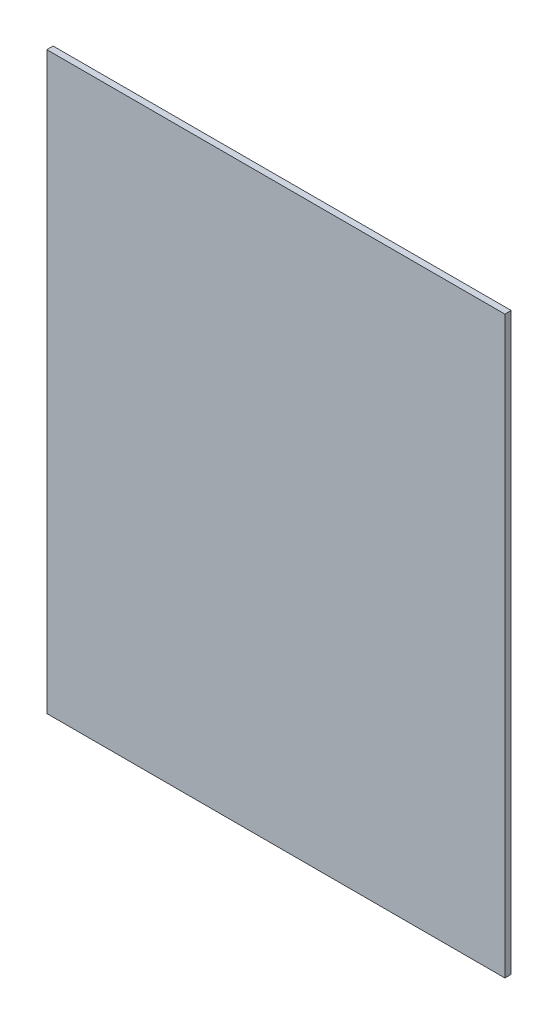
SolidWorks part; units mm, degrees
ref_plane "Płaszczyzna przednia" through (0, 0, 0) normal (0, 0, 1) x (1, 0, 0)
ref_plane "Płaszczyzna górna" through (0, 0, 0) normal (0, 1, 0) x (1, 0, 0)
ref_plane "Płaszczyzna prawa" through (0, 0, 0) normal (1, 0, 0) x (0, 0, -1)
sketch "Szkic1" plane through (0, 0, 0) normal (0, 0, 1) x (1, 0, 0)
  line L1 (72.5, 91) -> (-72.5, 91)
  line L2 (72.5, 91) -> (72.5, -91)
  line L3 (72.5, -91) -> (-72.5, -91)
  line L4 (-72.5, 91) -> (-72.5, -91)
  line L5 (72.5, 91) -> (-72.5, -91) construction
  line L6 (72.5, -91) -> (-72.5, 91) construction
  point P0 (0, 0)
  dimension "D1" = 145
  dimension "D2" = 182
extrude "Dodanie-wyciągnięcie1" add sketch "Szkic1" along normal blind 2
